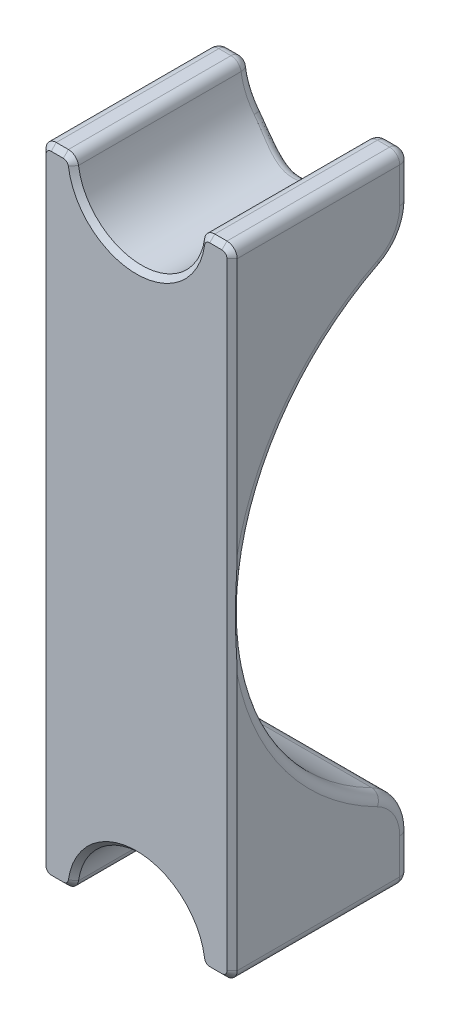
SolidWorks part; units mm, degrees
ref_plane "Front Plane" through (0, 0, 0) normal (1, 0, 0) x (0, 1, 0)
ref_plane "Top Plane" through (0, 0, 0) normal (0, 0, 1) x (0, 1, 0)
ref_plane "Right Plane" through (0, 0, 0) normal (0, 1, 0) x (-1, 0, 0)
sketch "Sketch1" plane through (0, 0, 0) normal (1, 0, 0) x (0, 1, 0)
  line L0 (-15.875, 0) -> (-15.875, 12.7) construction
  line L1 (15.875, 0) -> (15.875, 12.7) construction
  line L2 (13.208, 0) -> (13.208, 12.7)
  line L3 (-13.208, 0) -> (-13.208, 12.7)
  line L4 (18.542, 0) -> (18.542, 12.7)
  line L5 (-18.542, 0) -> (-18.542, 12.7)
  line L6 (-15.875, 0) -> (-15.875, 15.1154) construction
  line L7 (-18.542, 0) -> (-18.542, 15.1154) construction
  line L8 (-13.208, 0) -> (-13.208, 15.1154) construction
  line L9 (13.208, 12.7) -> (18.542, 12.7) construction
  line L10 (-13.208, 12.7) -> (-18.542, 12.7) construction
  circle A0 centre (0, 0) radius 12.7 construction
  arc A1 (-15.875, 0) -> (15.875, 0) centre (0, 0) ccw construction
  arc A2 (-13.208, 0) -> (13.208, 0) centre (0, 0) ccw
  arc A3 (-18.542, 0) -> (18.542, 0) centre (0, 0) ccw
  point P3 (15.875, 12.7)
  dimension "D1" = 25.4
  dimension "D4" = 31.75
  dimension "D2" = 5.334
sketch "Sketch2" plane through (0, 0, 0) normal (1, 0, 0) x (0, 1, 0)
  line L0 (-15.875, 13.208) -> (15.875, 13.208)
  line L2 (-15.875, 13.208) -> (-15.875, 4.3437)
  line L3 (-15.875, 0) -> (-15.875, 12.7) construction
  line L4 (-15.875, 4.3437) -> (-13.5968, 4.3437)
  line L5 (0, 0) -> (0, 12.7) construction
  line L6 (15.875, 4.3437) -> (13.5968, 4.3437)
  line L8 (15.875, 13.208) -> (15.875, 4.3437)
  line L9 (-11.9341, 4.3437) -> (0, 0) construction
  line L10 (0, 0) -> (-15.875, 0) construction
  arc A0 (11.3307, 5.7364) -> (-11.3307, 5.7364) centre (0, 0) ccw
  arc A1 (13.5968, 4.3437) -> (11.3307, 5.7364) centre (13.5968, 6.8837) cw
  arc A2 (-13.5968, 4.3437) -> (-11.3307, 5.7364) centre (-13.5968, 6.8837) ccw
  point P1 (0, 12.319)
  point P3 (17.3427, 13.208)
  point P4 (-15.254, 13.208)
  point P7 (0, 12.7)
  point P23 (11.9341, 4.3437)
  point P27 (-17.2793, 13.208)
  dimension "D3" = 2.54
  dimension "D1" = 12.7
  dimension "D2" = 20
  dimension "D4" = 0.508
extrude "Boss-Extrude1" add sketch "Sketch2" along normal mid plane 9.525
sketch "Sketch3" plane through (0, 0, 13.208) normal (0, 0, 1) x (1, 0, 0)
  line L1 (-4.7625, 0) -> (0, 0) construction
  line L3 (-4.7625, 15.875) -> (-4.7625, -15.875) construction
  line L4 (0, 13.208) -> (0, 18.542) construction
  line L5 (0, 13.208) -> (0, 18.542) construction
  line L6 (0, -18.542) -> (0, 18.542) construction
  circle A0 centre (0, 15.875) radius 3.175
  circle A1 centre (0, -15.875) radius 3.175
  point P2 (0, 0)
  point P3 (-0.084, 16.6393)
  point P6 (0, 0)
  point P11 (0, 12.7)
  point P13 (0, 0)
  point P16 (0, 0)
  point P17 (0, 16.7126)
  point P20 (0, 0)
  point P21 (0, 15.875)
  dimension "D1" = 6.35
extrude "Cut-Extrude1" cut sketch "Sketch3" against normal through all both and the other way through all
fillet "Fillet1" radius 0.508 8 edges at (4.7625, 15.875, 8.7758) (4.7625, -15.875, 8.7758) (3.175, -15.875, 8.7758) (-3.175, -15.875, 8.7758) (-4.7625, 15.875, 8.7758) (-3.175, 15.875, 8.7758) (3.175, 15.875, 8.7758) (-4.7625, -15.875, 8.7758)
chamfer "Chamfer1" distance 0.254 angle 45 16 edges at (4.7625, 0, 13.208) (4.6137, 15.7262, 13.208) (4.6137, -15.7262, 13.208) (3.9511, 15.875, 13.208) (3.9511, -15.875, 13.208) (3.3143, 15.7502, 13.208) (3.3143, -15.7502, 13.208) (0, 12.7, 13.208) (0, -12.7, 13.208) (-3.3143, 15.7502, 13.208) (-3.3143, -15.7502, 13.208) (-3.9511, 15.875, 13.208) (-3.9511, -15.875, 13.208) (-4.6137, 15.7262, 13.208) (-4.6137, -15.7262, 13.208) (-4.7625, 0, 13.208)
fillet "Fillet2" radius 0.508 28 edges at (-4.7625, -12.2668, 4.7197) (-4.7625, -14.4819, 4.3437) (-4.6137, -15.7262, 4.3437) (-3.9511, -15.875, 4.3437) (-3.3143, -15.7502, 4.3437) (-2.8317, -14.439, 4.3437) (0.374, -12.7221, 4.499) (2.8317, -14.439, 4.3437) (3.3143, -15.7502, 4.3437) (3.9511, -15.875, 4.3437) (4.6137, -15.7262, 4.3437) (4.7625, -14.4819, 4.3437) (4.7625, -12.2668, 4.7197) (4.7625, 0, 12.7) (4.7625, 12.2668, 4.7197) (4.7625, 14.4819, 4.3437) (4.6137, 15.7262, 4.3437) (3.9511, 15.875, 4.3437) (3.3143, 15.7502, 4.3437) (2.8317, 14.439, 4.3437) (-0.374, 12.7221, 4.499) (-2.8317, 14.439, 4.3437) (-3.3143, 15.7502, 4.3437) (-3.9511, 15.875, 4.3437) (-4.6137, 15.7262, 4.3437) (-4.7625, 14.4819, 4.3437) (-4.7625, 12.2668, 4.7197) (-4.7625, 0, 12.7)
